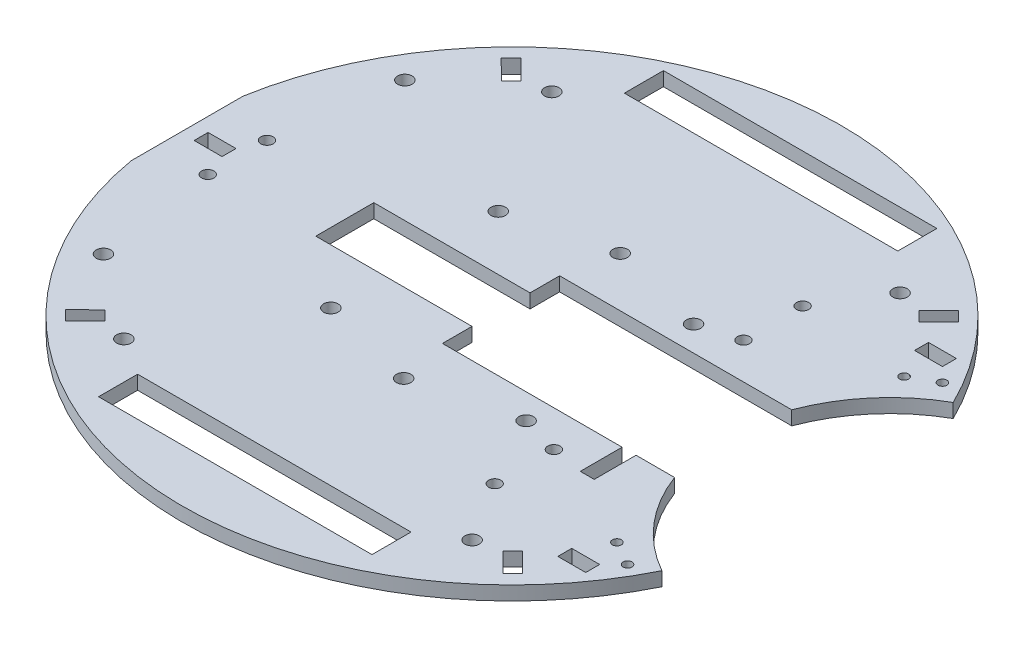
SolidWorks part; units mm, degrees
material "Acrylic (Medium-high impact)"
ref_plane "Front Plane" through (0, 0, 0) normal (0, 0, 1) x (1, 0, 0)
ref_plane "Top Plane" through (0, 0, 0) normal (0, 1, 0) x (1, 0, 0)
ref_plane "Right Plane" through (0, 0, 0) normal (1, 0, 0) x (0, 0, -1)
sketch "Sketch1" plane through (0, 0, 0) normal (0, 1, 0) x (1, 0, 0)
  line L0 (67.2709, 33.1606) -> (86.0323, 0) construction
  line L1 (86.0323, 0) -> (67.2709, -33.1606) construction
  line L2 (0, 65.5895) -> (0, 75) construction
  line L3 (-31.115, -54.0813) -> (31.115, -54.0813)
  line L4 (-31.115, -54.0813) -> (-31.115, -62.9713)
  line L5 (-31.115, -62.9713) -> (31.115, -62.9713)
  line L6 (31.115, -54.0813) -> (31.115, -62.9713)
  line L7 (-31.115, 65.5895) -> (31.115, 65.5895)
  line L8 (-31.115, 65.5895) -> (-31.115, 56.6995)
  line L9 (-31.115, 56.6995) -> (31.115, 56.6995)
  line L10 (31.115, 65.5895) -> (31.115, 56.6995)
  line L12 (31.115, -62.9713) -> (33.224, -67.2396) construction
  line L13 (-62.4869, 6.731) -> (-62.4869, -6.731) construction
  line L14 (-62.4869, 0) -> (-73.9169, 0) construction
  line L16 (58.9661, -42.1806) -> (52.6161, -42.1806)
  line L17 (58.9661, -42.1806) -> (58.9661, -39.0056)
  line L18 (58.9661, -39.0056) -> (52.6161, -39.0056)
  line L19 (52.6161, -42.1806) -> (52.6161, -39.0056)
  line L20 (58.9661, 42.1806) -> (52.6161, 42.1806)
  line L21 (58.9661, 42.1806) -> (58.9661, 39.0056)
  line L22 (60.7114, 44.0354) -> (67.2709, 33.1606) construction
  line L23 (0, 0) -> (86.0323, 0) construction
  line L24 (52.6161, 42.1806) -> (52.6161, 39.0056)
  line L25 (58.9661, 39.0056) -> (52.6161, 39.0056)
  line L28 (-39.6269, -48.6985) -> (0, -24.638) construction
  line L29 (0, -24.638) -> (39.6269, -48.6985) construction
  line L30 (-39.6269, -48.6985) -> (39.6269, -48.6985) construction
  line L31 (0, -24.638) -> (0, -48.6985) construction
  line L32 (-2.4867, 6.604) -> (-2.4867, 13.335) construction
  line L33 (38.4073, -13.335) -> (-2.4867, -13.335) construction
  line L34 (-2.4867, -13.335) -> (-2.4867, -6.604) construction
  line L35 (-2.4867, 13.335) -> (38.4073, 13.335) construction
  line L36 (38.4073, 13.335) -> (41.5823, 13.335)
  line L37 (45.2673, -47.3326) -> (49.7661, -51.814)
  line L38 (45.2673, -47.3326) -> (47.508, -45.0831)
  line L39 (49.7661, -51.814) -> (52.0068, -49.5645)
  line L40 (47.508, -45.0831) -> (52.0068, -49.5645)
  line L41 (-58.6769, -34.29) -> (-58.6769, 34.29) construction
  line L42 (0, 0) -> (-16.51, 0) construction
  line L43 (-58.6769, 0) -> (-62.4869, 0) construction
  line L44 (41.5823, 13.335) -> (50.3421, 13.335)
  line L45 (41.5823, -13.335) -> (46.2813, -13.335)
  line L46 (-2.4867, -6.604) -> (-2.4867, -13.335)
  line L47 (-73.9169, 12.7) -> (-73.9169, -12.7)
  line L48 (38.4073, 13.335) -> (-2.4867, 13.335)
  line L49 (-2.4867, 13.335) -> (-2.4867, 6.604)
  line L50 (-2.4867, -13.335) -> (38.4073, -13.335)
  line L51 (46.2813, -13.335) -> (50.3421, -13.335)
  line L52 (-2.4867, 0) -> (-38.0467, 0) construction
  line L53 (-2.4867, 6.604) -> (-38.0467, 6.604)
  line L54 (14.856, 13.335) -> (14.856, 0) construction
  line L55 (-2.4867, -6.604) -> (-38.0467, -6.604)
  line L56 (-38.0467, 6.604) -> (-38.0467, -6.604)
  line L57 (14.856, 0) -> (14.856, -13.335) construction
  line L58 (45.2673, -47.3326) -> (52.0068, -49.5645) construction
  line L59 (49.7661, -51.814) -> (47.508, -45.0831) construction
  line L60 (41.5823, -13.335) -> (41.5823, -22.86)
  line L61 (41.5823, -22.86) -> (38.4073, -22.86)
  line L62 (38.4073, -13.335) -> (38.4073, -22.86)
  line L63 (46.3876, -46.2078) -> (0, 0) construction
  line L64 (50.8864, -50.6893) -> (53.1359, -52.93) construction
  line L65 (-45.2673, -47.3326) -> (-47.508, -45.0831)
  line L66 (-45.2673, -47.3326) -> (-49.7661, -51.814)
  line L67 (-49.7661, -51.814) -> (-52.0068, -49.5645)
  line L68 (-47.508, -45.0831) -> (-52.0068, -49.5645)
  line L69 (-47.508, 45.0831) -> (-52.0068, 49.5645)
  line L70 (-45.2673, 47.3326) -> (-47.508, 45.0831)
  line L71 (-45.2673, 47.3326) -> (-49.7661, 51.814)
  line L72 (-49.7661, 51.814) -> (-52.0068, 49.5645)
  line L73 (47.508, 45.0831) -> (52.0068, 49.5645)
  line L74 (45.2673, 47.3326) -> (47.508, 45.0831)
  line L75 (45.2673, 47.3326) -> (49.7661, 51.814)
  line L76 (49.7661, 51.814) -> (52.0068, 49.5645)
  line L77 (-73.9169, 0) -> (-70.7419, 0) construction
  line L78 (-70.7419, 1.5875) -> (-64.3919, 1.5875)
  line L79 (-70.7419, 1.5875) -> (-70.7419, -1.5875)
  line L80 (-70.7419, -1.5875) -> (-64.3919, -1.5875)
  line L81 (-64.3919, 1.5875) -> (-64.3919, -1.5875)
  arc A0 (67.2709, 33.1606) -> (-73.9169, 12.7) centre (0, 0) ccw
  arc A1 (67.2709, -33.1606) -> (55.0862, -22.225) centre (86.0323, 0) cw
  circle A2 centre (-62.4869, 6.731) radius 1.397
  circle A3 centre (-62.4869, -6.731) radius 1.397
  circle A4 centre (-39.6269, -48.6985) radius 1.651
  circle A5 centre (39.6269, -48.6985) radius 1.651
  circle A6 centre (39.6269, 48.6985) radius 1.651
  circle A7 centre (0, -24.638) radius 1.651
  circle A8 centre (-39.6269, 48.6985) radius 1.651
  circle A9 centre (0, 24.638) radius 1.651
  circle A10 centre (31.115, -35.0313) radius 1.397
  arc A11 (55.0862, -22.225) -> (50.3421, -13.335) centre (86.0323, 0) cw
  circle A12 centre (-58.6769, 34.29) radius 1.651
  circle A13 centre (62.1411, -35.8306) radius 1.016
  circle A14 centre (56.5708, -32.6791) radius 1.016
  circle A15 centre (-58.6769, -34.29) radius 1.651
  arc A16 (50.3421, 13.335) -> (67.2709, 33.1606) centre (86.0323, 0) cw
  arc A17 (-73.9169, -12.7) -> (67.2709, -33.1606) centre (0, 0) ccw
  circle A18 centre (31.115, -21.5693) radius 1.397
  circle A19 centre (31.115, 35.0313) radius 1.397
  circle A20 centre (31.115, 21.5693) radius 1.397
  circle A25 centre (62.1411, 35.8306) radius 1.016
  circle A26 centre (56.5708, 32.6791) radius 1.016
  circle A27 centre (56.5708, 32.6791) radius 1.016 construction
  circle A28 centre (22.2783, 19.05) radius 1.651
  circle A29 centre (22.2783, -19.05) radius 1.651
  circle A30 centre (-22.1717, -19.05) radius 1.651
  circle A31 centre (-22.1717, 19.05) radius 1.651
  circle A32 centre (22.2783, 19.05) radius 1.651 construction
  point P50 (41.5823, 0)
  point P56 (47.9323, 0)
  point P63 (48.637, -48.4486)
  dimension "D1" = 150
  dimension "D7" = 11.43
  dimension "D8" = 2.794
  dimension "D14" = 24.0605
  dimension "D16" = 3.302
  dimension "D22" = 13.208
  dimension "D27" = 3.302
  dimension "D34" = 2.794
  dimension "D2" = 121
  dimension "D3" = 38.1
  dimension "D4" = 62.23
  dimension "D5" = 8.89
  dimension "D9" = 13.462
  dimension "D10" = 6.35
  dimension "D11" = 3.175
  dimension "D12" = 3.175
  dimension "D13" = 3.175
  dimension "D15" = 3.175
  dimension "D18" = 25.4
  dimension "D19" = 26.67
  dimension "D20" = 44.069
  dimension "D21" = 17.3428
  dimension "D23" = 38.1
  dimension "D24" = 9.525
  dimension "D25" = 15.24
  dimension "D26" = 68.58
  dimension "D28" = 44.45
  dimension "D29" = 35.56
  dimension "D30" = 6.35
  dimension "D31" = 88.519
  dimension "D32" = 16.51
  dimension "D33" = 13.462
  dimension "D35" = 19.05
  dimension "D37" = 3.175
  dimension "D39" = 3.175
extrude "Boss-Extrude1" add sketch "Sketch1" along normal blind 3.175
equation "\"Diameter\"= 2.75"
